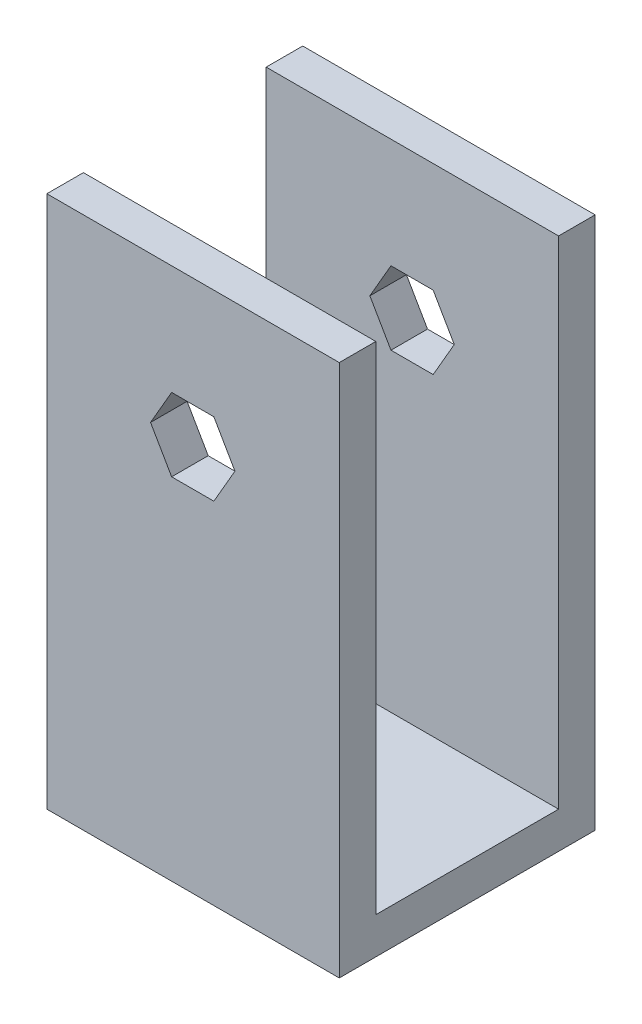
SolidWorks part; units mm, degrees
ref_plane "Front Plane" through (0, 0, 0) normal (0, 0, 1) x (1, 0, 0)
ref_plane "Top Plane" through (0, 0, 0) normal (0, 1, 0) x (1, 0, 0)
ref_plane "Right Plane" through (0, 0, 0) normal (1, 0, 0) x (0, 0, -1)
sketch "Sketch1" plane through (0, 0, 0) normal (0, 0, 1) x (1, 0, 0)
  line L1 (-990.7207, 634.9497) -> (-939.9207, 634.9497)
  line L2 (-990.7207, 634.9497) -> (-990.7207, 542.3575)
  line L3 (-990.7207, 542.3575) -> (-939.9207, 542.3575)
  line L4 (-939.9207, 634.9497) -> (-939.9207, 542.3575)
  line L5 (-972.7075, 609.5497) -> (-969.0414, 603.1997)
  line L6 (-969.0414, 603.1997) -> (-961.709, 603.1997)
  line L7 (-961.709, 603.1997) -> (-958.0428, 609.5497)
  line L8 (-958.0428, 609.5497) -> (-961.709, 615.8997)
  line L9 (-961.709, 615.8997) -> (-969.0414, 615.8997)
  line L10 (-990.7207, 542.3575) -> (-939.9207, 542.3575)
  line L11 (-990.7207, 542.3575) -> (-990.7207, 548.7075)
  line L12 (-990.7207, 548.7075) -> (-939.9207, 548.7075)
  line L13 (-939.9207, 542.3575) -> (-939.9207, 548.7075)
  line L14 (-969.0414, 615.8997) -> (-972.7075, 609.5497)
  circle A1 centre (-965.3752, 609.5497) radius 6.35 construction
  dimension "D2" = 25.4
  dimension "D1" = 50.8
  dimension "D3" = 6.35
  dimension "D4" = 12.7
extrude "Boss-Extrude1" add sketch "Sketch1" along normal blind 6.35 contours L2 L12 L4 L1 region at (-965.3189, 591.245, 0)
extrude "Boss-Extrude2" add sketch "Sketch1<3>" along normal blind 38.1 contours L12 L2 L3 L4 region at (-965.3207, 545.5325, 0)
sketch "Sketch1<3>" plane through (0, 0, 0) normal (0, 0, 1) x (1, 0, 0) same geometry as "Sketch1"
sketch "Sketch2" plane through (0, 0, 38.1) normal (0, 0, 1) x (1, 0, 0)
  line L0 (-961.709, 603.1997) -> (-958.0428, 609.5497) construction
  line L1 (-969.0414, 603.1997) -> (-961.709, 603.1997) construction
  line L2 (-972.7075, 609.5497) -> (-969.0414, 603.1997) construction
  line L3 (-969.0414, 615.8997) -> (-972.7075, 609.5497) construction
  line L4 (-990.7207, 634.9497) -> (-990.7207, 542.3575)
  line L5 (-939.9207, 634.9497) -> (-990.7207, 634.9497)
  line L6 (-939.9207, 542.3575) -> (-939.9207, 634.9497)
  line L7 (-990.7207, 542.3575) -> (-939.9207, 542.3575)
  line L8 (-990.7207, 634.9497) -> (-990.7207, 542.3575)
  line L9 (-939.9207, 634.9497) -> (-990.7207, 634.9497)
  line L10 (-939.9207, 542.3575) -> (-939.9207, 634.9497)
  line L11 (-990.7207, 542.3575) -> (-939.9207, 542.3575)
  line L12 (-990.7207, 634.9497) -> (-990.7207, 548.7075)
  line L13 (-990.7207, 548.7075) -> (-939.9207, 548.7075)
  line L14 (-939.9207, 548.7075) -> (-939.9207, 634.9497)
  line L15 (-939.9207, 634.9497) -> (-990.7207, 634.9497)
  line L16 (-990.7207, 634.9497) -> (-990.7207, 548.7075)
  line L17 (-990.7207, 548.7075) -> (-939.9207, 548.7075)
  line L18 (-939.9207, 548.7075) -> (-939.9207, 634.9497)
  line L19 (-939.9207, 634.9497) -> (-990.7207, 634.9497)
  line L20 (-961.709, 615.8997) -> (-969.0414, 615.8997) construction
  line L21 (-958.0428, 609.5497) -> (-961.709, 615.8997) construction
  line L22 (-961.709, 603.1997) -> (-958.0428, 609.5497)
  line L23 (-969.0414, 603.1997) -> (-961.709, 603.1997)
  line L24 (-972.7075, 609.5497) -> (-969.0414, 603.1997)
  line L25 (-969.0414, 615.8997) -> (-972.7075, 609.5497)
  line L26 (-961.709, 615.8997) -> (-969.0414, 615.8997)
  line L27 (-958.0428, 609.5497) -> (-961.709, 615.8997)
  line M5 (-939.9207, 548.7075) -> (-990.7207, 548.7075)
  line M6 (-990.7207, 548.7075) -> (-990.7207, 542.3575)
  line M7 (-990.7207, 542.3575) -> (-939.9207, 542.3575)
  line M8 (-939.9207, 542.3575) -> (-939.9207, 548.7075)
  dimension "D1" = 0
  dimension "D2" = 0
extrude "Boss-Extrude4" add sketch "Sketch2" along normal blind 6.35 contours L10 L9 L8 L27 L22 L23 L24 L25 L26 M5 | M8 M5 M6 M7 region at (-965.3189, 591.245, 38.1) region at (-965.3207, 545.5325, 38.1)
